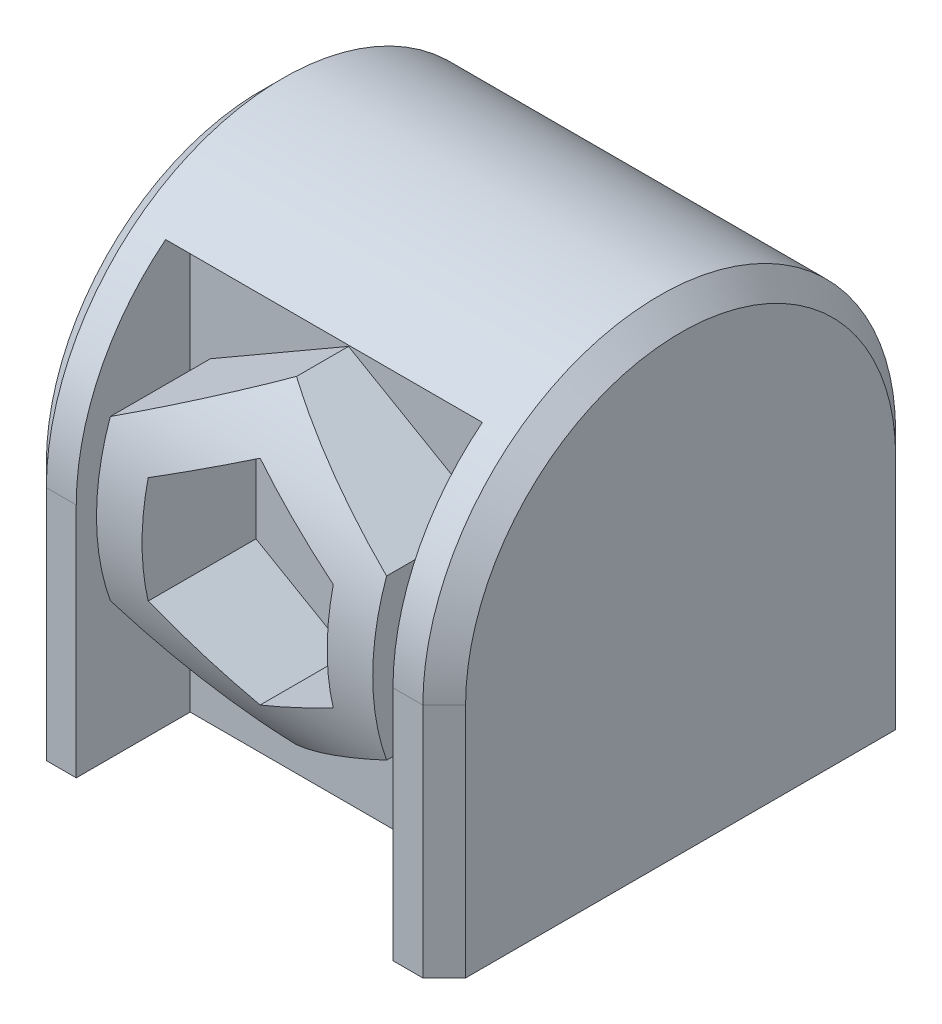
SolidWorks part; units mm, degrees
ref_plane "Front Plane" through (0, 0, 0) normal (0, 0, 1) x (1, 0, 0)
ref_plane "Top Plane" through (0, 0, 0) normal (0, 1, 0) x (1, 0, 0)
ref_plane "Right Plane" through (0, 0, 0) normal (1, 0, 0) x (0, 0, -1)
sketch "Sketch1" plane through (0, 0, 0) normal (1, 0, 0) x (0, 0, -1)
  line L0 (-10.541, 0) -> (-10.541, -10.541)
  line L1 (-10.541, -10.541) -> (10.541, -10.541)
  line L2 (10.541, -10.541) -> (10.541, 0)
  arc A0 (10.541, 0) -> (-10.541, 0) centre (0, 0) ccw
  dimension "D1" = 21.082
extrude "Boss-Extrude1" add sketch "Sketch1" along normal blind 18.6944 contours A0 L0 L1 L2
chamfer "Chamfer1" distance 0.9525 angle 45 6 edges at (0, -5.2705, -10.541) (0, -5.2705, 10.541) (0, 10.541, 0) (18.6944, -5.2705, -10.541) (18.6944, -5.2705, 10.541) (18.6944, 10.541, 0)
sketch "Sketch2" plane through (0, 0, 10.541) normal (0, 0, 1) x (1, 0, 0)
  line L0 (17.7419, -10.541) -> (0.9525, -10.541) construction
  line L1 (2.286, -10.541) -> (16.4084, -10.541)
  line L2 (2.286, -10.541) -> (2.286, 8.255)
  line L3 (2.286, 8.255) -> (16.4084, 8.255)
  line L4 (16.4084, -10.541) -> (16.4084, 8.255)
  line L5 (17.7419, 10.541) -> (0.9525, 10.541) construction
  line L6 (18.6944, 0) -> (18.6944, 9.5885) construction
  line L7 (0, 9.5885) -> (0, 0) construction
  dimension "D1" = 2.286
  dimension "D2" = 2.286
  dimension "D3" = 2.286
extrude "Cut-Extrude1" cut sketch "Sketch2" against normal blind 6.35
shell "Shell2" thickness 2.286 removed face at (9.3472, -1.143, 4.191)
sketch "Sketch3" plane through (0, 0, 4.191) normal (0, 0, 1) x (1, 0, 0)
  line L0 (16.4084, 0) -> (2.286, 0) construction
  line L1 (9.3472, 7.112) -> (3.188, 3.556)
  line L2 (3.188, 3.556) -> (3.188, -3.556)
  line L3 (3.188, -3.556) -> (9.3472, -7.112)
  line L4 (9.3472, -7.112) -> (15.5064, -3.556)
  line L5 (15.5064, -3.556) -> (15.5064, 3.556)
  line L6 (15.5064, 3.556) -> (9.3472, 7.112)
  line L8 (9.3472, 4.7656) -> (5.22, 2.3828)
  line L9 (5.22, 2.3828) -> (5.22, -2.3828)
  line L10 (5.22, -2.3828) -> (9.3472, -4.7656)
  line L11 (9.3472, -4.7656) -> (13.4744, -2.3828)
  line L12 (13.4744, -2.3828) -> (13.4744, 2.3828)
  line L13 (13.4744, 2.3828) -> (9.3472, 4.7656)
  circle A0 centre (9.3472, 0) radius 6.1592 construction
  circle A1 centre (9.3472, 0) radius 4.1272 construction
  dimension "D1" = 2.032
extrude "Boss-Extrude3" add sketch "Sketch3" along normal up to surface (5.7321 mm away) separate body up to face at (9.3472, 4.813, 4.5101)
sketch "Sketch4" plane through (0, 0, 4.191) normal (0, 0, 1) x (1, 0, 0)
  line L1 (2.286, -10.541) -> (16.7591, -10.541)
  line L2 (2.286, -10.541) -> (2.286, 8.8663)
  line L3 (2.286, 8.8663) -> (16.7591, 8.8663)
  line L4 (16.7591, -10.541) -> (16.7591, 8.8663)
extrude "Boss-Extrude4" add sketch "Sketch4" along normal blind 1.27 and the other way blind 0.9525
